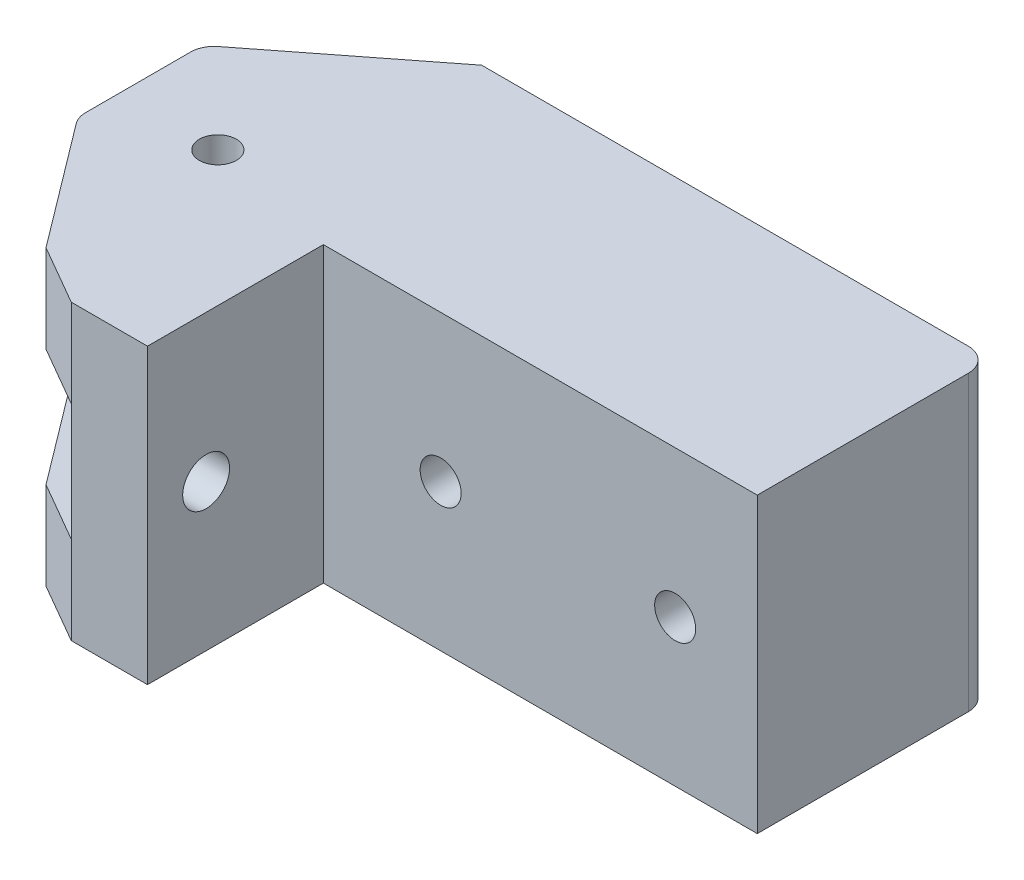
SolidWorks part; units mm, degrees
ref_plane "Front Plane" through (0, 0, 0) normal (0, 0, 1) x (1, 0, 0)
ref_plane "Top Plane" through (0, 0, 0) normal (0, 1, 0) x (1, 0, 0)
ref_plane "Right Plane" through (0, 0, 0) normal (1, 0, 0) x (0, 0, -1)
sketch "Sketch1" plane through (0, 0, 0) normal (0, 1, 0) x (1, 0, 0)
  line L0 (0, 0) -> (-43.5, 0)
  line L1 (-43.5, 0) -> (-43.5, -35) construction
  line L2 (-43.5, -35) -> (-37, -35)
  line L3 (-37, -35) -> (-37, -20)
  line L4 (-37, -20) -> (0, -20)
  line L5 (0, -20) -> (0, 0)
  line L6 (-43.5, 0) -> (-56.8853, -10.4577)
  line L7 (-56.8853, -10.4577) -> (-56.8853, -21.0577)
  line L8 (-56.8853, -21.0577) -> (-48.5962, -32.0577)
  line L9 (-48.5962, -32.0577) -> (-43.5, -35)
  line L10 (-43.5, -17.5) -> (-48.5, -17.5) construction
  circle A0 centre (-48.5, -17.5) radius 1.575
  dimension "D11" = 3.15
  dimension "D1" = 43.5
  dimension "D2" = 35
  dimension "D3" = 20
  dimension "D4" = 37
  dimension "D5" = 30
  dimension "D6" = 38
  dimension "D7" = 10.6
  dimension "D8" = 37
  dimension "D9" = 11
  dimension "D10" = 5
extrude "Boss-Extrude1" add sketch "Sketch1" along normal mid plane 25
sketch "Sketch2" plane through (0, 0, 35) normal (0, 0, 1) x (1, 0, 0)
  line L0 (-43.5, 12.5) -> (-43.5, -12.5) construction
  line L1 (-43.5, -5) -> (-56.8853, -5)
  line L2 (-43.5, -5) -> (-43.5, 5)
  line L3 (-43.5, 5) -> (-56.8853, 5)
  line L4 (-56.8853, -5) -> (-56.8853, 5)
  line L5 (-56.8853, 12.5) -> (-56.8853, -12.5) construction
  line L6 (-56.8853, 12.5) -> (-48.5962, 12.5) construction
  dimension "D1" = 7.5
  dimension "D2" = 10
extrude "Cut-Extrude1" cut sketch "Sketch2" against normal through all
sketch "Sketch3" plane through (0, 0, 20) normal (0, 0, 1) x (1, 0, 0)
  line L1 (0, 0) -> (-27, 0) construction
  line L2 (-37, 12.5) -> (-37, -12.5) construction
  circle A0 centre (-27, 0) radius 1.75
  circle A1 centre (-7, 0) radius 1.75
  dimension "D1" = 3.5
  dimension "D2" = 20
  dimension "D3" = 10
extrude "Cut-Extrude2" cut sketch "Sketch3" against normal blind 25
sketch "Sketch4" plane through (0, 0, 0) normal (0, 0, -1) x (-1, 0, 0)
  circle A0 centre (7, 0) radius 4
  circle A2 centre (27, 0) radius 4
extrude "Cut-Extrude3" cut sketch "Sketch4" against normal blind 4
fillet "Fillet1" radius 2 5 edges at (0, 0, 0) (-56.8853, 8.75, 10.4577) (-56.8853, 8.75, 21.0577) (-56.8853, -8.75, 21.0577) (-56.8853, -8.75, 10.4577)
sketch "Sketch5" plane through (-43.5, 0, 0) normal (-1, 0, 0) x (0, 0, 1)
  line L0 (30, -12.5) -> (30, 12.5) construction
  line L3 (35, -5) -> (35, 5) construction
  line L4 (21.5922, 12.5) -> (32.0577, 12.5) construction
  line L5 (21.5922, -12.5) -> (32.0577, -12.5) construction
  circle A0 centre (30, 0) radius 2
  dimension "D1" = 4
  dimension "D2" = 5
sketch "Sketch6" plane through (0, 12.5, 0) normal (0, 1, 0) x (1, 0, 0)
  line L0 (-37, -35) -> (-37, -20)
extrude "Cut-Extrude4" cut sketch "Sketch5" against normal blind 10
sketch "Sketch7" plane through (-43.5, 0, 0) normal (-1, 0, 0) x (0, 0, 1)
  circle A0 centre (30, 0) radius 3.575
  dimension "D1" = 7.15
extrude "Cut-Extrude5" cut sketch "Sketch7" against normal blind 3.5
